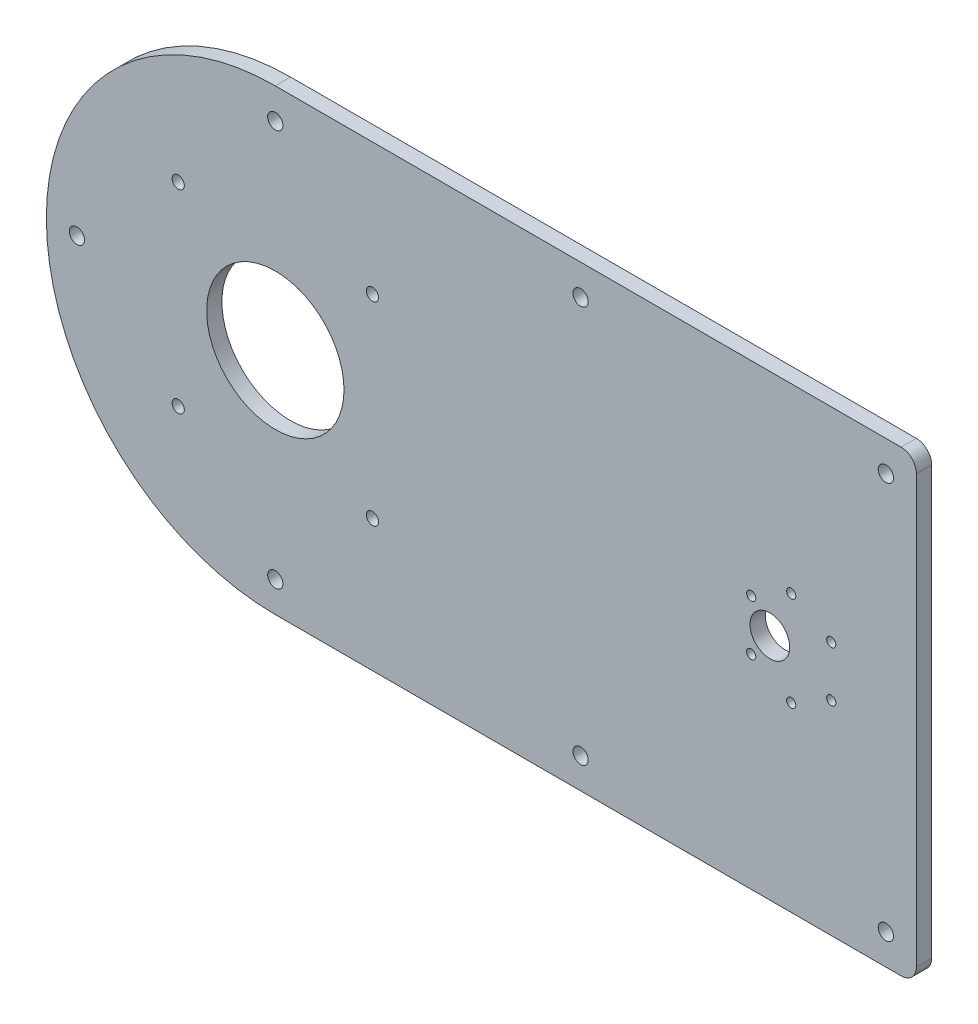
SolidWorks part; units mm, degrees
ref_plane "Front Plane" through (0, 0, 0) normal (0, 0, 1) x (1, 0, 0)
ref_plane "Top Plane" through (0, 0, 0) normal (0, 1, 0) x (1, 0, 0)
ref_plane "Right Plane" through (0, 0, 0) normal (1, 0, 0) x (0, 0, -1)
sketch "Sketch1" plane through (0, 0, 0) normal (0, 0, 1) x (1, 0, 0)
  line L1 (30.0007, 92.5455) -> (235.0007, 92.5455)
  line L3 (30.0007, -57.4545) -> (235.0007, -57.4545)
  line L4 (240.0007, 87.5455) -> (240.0007, -52.4545)
  arc A0 (235.0007, -57.4545) -> (240.0007, -52.4545) centre (235.0007, -52.4545) ccw
  arc A1 (235.0007, 92.5455) -> (240.0007, 87.5455) centre (235.0007, 87.5455) cw
  arc A2 (30.0007, 92.5455) -> (30.0007, -57.4545) centre (30.0007, 17.5455) ccw
  circle A7 centre (-34.9993, 17.5455) radius 2.5
  circle A10 centre (30.0007, -47.4545) radius 2.5
  circle A11 centre (30.0007, 82.5455) radius 2.5
  circle A12 centre (230.0007, -47.4545) radius 2.5
  circle A13 centre (230.0007, 82.5455) radius 2.5
  circle A15 centre (130.0007, 82.5455) radius 2.5
  circle A16 centre (130.0007, -47.4545) radius 2.5
  circle A18 centre (30.0007, 17.5455) radius 22.5
  circle A23 centre (61.8157, 49.3605) radius 2
  circle A24 centre (61.8157, -14.2695) radius 2
  circle A25 centre (-1.8143, -14.2695) radius 2
  circle A26 centre (-1.8143, 49.3605) radius 2
  circle A27 centre (192.0007, 17.5455) radius 6.5
  circle A31 centre (199.0007, 33.0455) radius 1.5
  circle A32 centre (199.0007, 2.0455) radius 1.5
  circle A33 centre (185.8934, 25.8189) radius 1.5
  circle A34 centre (212.108, 25.8189) radius 1.5
  circle A35 centre (212.108, 9.2721) radius 1.5
  circle A36 centre (185.8934, 9.2721) radius 1.5
  point P2 (30.0007, 17.5455)
  point P12 (192.0007, 17.5455)
  point P14 (30.0007, 17.5455)
  point P21 (-34.9993, 17.5455)
  point P23 (30.0007, 17.5455)
  point P53 (30.0007, 17.5455)
  point P54 (30.0007, 17.5455)
  dimension "D1" = 5
  dimension "D2" = 13
  dimension "D3" = 45
  dimension "D4" = 5
  dimension "D5" = 5
  dimension "D6" = 5
  dimension "D7" = 5
  dimension "D8" = 5
  dimension "D9" = 5
  dimension "D10" = 5
  dimension "D11" = 4
  dimension "D12" = 4
  dimension "D13" = 4
  dimension "D14" = 4
  dimension "D15" = 3
  dimension "D16" = 3
  dimension "D17" = 3
  dimension "D18" = 3
  dimension "D19" = 3
  dimension "D20" = 3
extrude "Boss-Extrude1" add sketch "Sketch1" along normal blind 5
